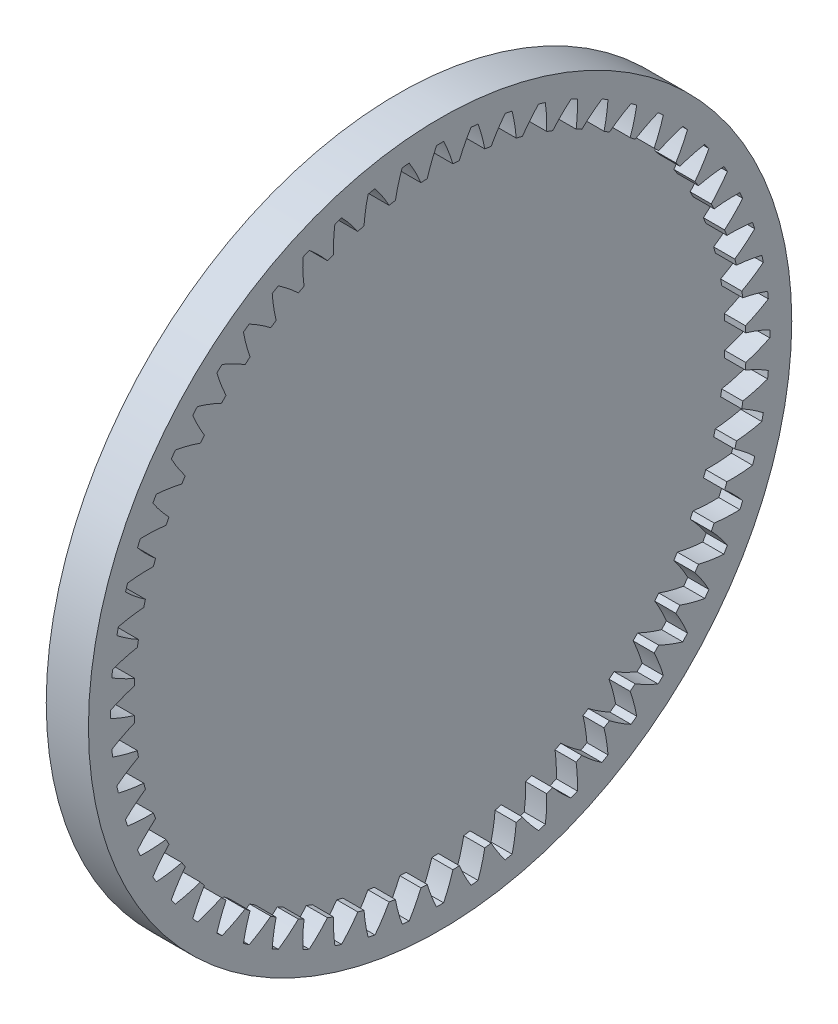
SolidWorks part; units mm, degrees
ref_plane "Plane1" through (0, 0, 0) normal (0, 0, 1) x (1, 0, 0)
ref_plane "Plane2" through (0, 0, 0) normal (0, 1, 0) x (1, 0, 0)
ref_plane "Plane3" through (0, 0, 0) normal (1, 0, 0) x (0, 0, -1)
other "Configuration Table"
sketch "HoldingSke" plane through (0, 0, 0) normal (0, 1, 0) x (1, 0, 0)
  line L0 (0, 0) -> (0.1667, -0.2887)
  line L1 (-15, 0) -> (100, 0) construction
  line L2 (0, 0) -> (-2.1039, 2.3779)
  line L3 (0, 0) -> (-11.863, 4.5341)
  line L4 (0, 0) -> (4.318, 7.479)
  line L5 (0, 0) -> (-23.7986, -8.8762)
  line L6 (0, 0) -> (-10.5278, -7.1032)
  line L7 (-2.1039, 2.3779) -> (3.3635, 27.1825)
  line L8 (-76.2, 5.3779) -> (-54.61, 5.3779)
  line L9 (-71.009, 38.7566) -> (-53.1078, 45.2721)
  line L10 (-76.2, 71.12) -> (104.1128, 71.12)
  line L11 (0, 0) -> (-12, 0)
  line L12 (-76.2, 101.6) -> (-76.093, 101.6)
  line L13 (24.9733, 27.94) -> (52.9518, 28.4284)
  line L14 (24.9733, 27.94) -> (24.9743, 27.94)
  line L15 (24.9733, 27.94) -> (100.4006, 29.5858)
  circle A0 centre (0, 0) radius 100
  circle A1 centre (0, 0) radius 12.7
  circle A2 centre (0, 0) radius 12.7
  dimension "Num_teeth" = 60
  dimension "Pitch_radius" = 180.3128
  dimension "Width" = 12
  dimension "Diameter" = 200
sketch "BasProSke" plane through (0, 0, 0) normal (0, 1, 0) x (1, 0, 0)
  line L0 (-10, 0) -> (60, 0) construction
  line L1 (0, 87) -> (0, 100)
  line L2 (0, 87) -> (12, 87)
  line L3 (12, 87) -> (12, 100)
  line L4 (12, 100) -> (0, 100)
  dimension "Thickness" = 12
  dimension "Diameter" = 200
revolve "Base-Revolve" add sketch "BasProSke" angle 360 about L0
sketch "TooCutSke" plane through (0, 0, 0) normal (1, 0, 0) x (0, 0, -1)
  line L3 (2.6234, 89.9618) -> (2.6234, 53.6633) construction
  line L4 (0, 0) -> (0, 59.563) construction
  line L5 (0, 0) -> (-3.576, 68.2339) construction
  line L6 (-39.5068, 74.1491) -> (33.8074, 77.9913) construction
  circle A0 centre (0, 0) radius 90 construction
  circle A1 centre (0, 0) radius 93.751 construction
  circle A2 centre (0, 0) radius 76.1151 construction
  circle A3 centre (0, 0) radius 86.9746 construction
  arc A4 (3.6494, 86.898) -> (1.0021, 93.7456) centre (-39.5068, 74.1491) ccw
  arc A5 (3.6494, 86.898) -> (-3.6494, 86.898) centre (0, 0) ccw
  arc A6 (1.0021, 93.7456) -> (-1.0021, 93.7456) centre (0, 0) ccw
  arc A7 (-1.0021, 93.7456) -> (-3.6494, 86.898) centre (39.5068, 74.1491) ccw
extrude "ToothCut" cut sketch "TooCutSke" along normal through all
fillet "Breaks" [suppressed] radius 0.3
fillet "RootFillets" [suppressed] radius 0.751
pattern_circular "TeethCuts" count 60 every 6 about axis through (-10, 0, 0) along (1, 0, 0) of "RootFillets", "Breaks", "ToothCut"
sketch "Sketch1" plane through (0, 0, 0) normal (-1, 0, 0) x (0, 0, 1)
  circle A0 centre (0, 0) radius 100
extrude "Boss-Extrude1" add sketch "Sketch1" against normal blind 6
equation "' \"Module@HoldingSke\" = 6.35"
equation "' \"Num_teeth@HoldingSke\" = 24"
equation "' \"Ap@HoldingSke\" =  14.5"
equation "' \"Ap@HoldingSke\" = 14.5"
equation "' \"Width@HoldingSke\" = 12"
equation "' \"Diameter@HoldingSke\" = 8 * 25.4"
equation "' \"Show_teeth@HoldingSke\" = 100"
equation "' \"Backlash@HoldingSke\" = 0.009 * 25.4"
equation "' \"Addendum_fac@HoldingSke\" = 1.0"
equation "' \"Dedendum_fac@HoldingSke\" = 1.25"
equation "' \"Dedendum_add@HoldingSke\" = 0.00005 * 25.4"
equation "' \"Clearance_fac@HoldingSke\" = 0.25"
equation "\"Pitch@HoldingSke\" = 1 / \"Module@HoldingSke\" "
equation "\"Overcut_dia@TooCutSke\" = (\"Num_teeth@HoldingSke\" - 2 * \"Addendum_fac@HoldingSke\") / \"Pitch@HoldingSke\" - 0.002 * 25.4"
equation "\"Pitch_dia@TooCutSke\" = \"Num_teeth@HoldingSke\" / \"Pitch@HoldingSke\""
equation "\"Base_dia@TooCutSke\" = \"Num_teeth@HoldingSke\" / \"Pitch@HoldingSke\" * cos((\"Ap@HoldingSke\"  * 3.14159265 / 180)) * 0.90"
equation "\"Root_dia@TooCutSke\" = \"Num_teeth@HoldingSke\"  / \"Pitch@HoldingSke\" + 2 *  \"Dedendum_fac@HoldingSke\"/ \"Pitch@HoldingSke\" + \"Dedendum_add@HoldingSke\" * 2"
equation "\"Half_ang@TooCutSke\" = 180 / \"Num_teeth@HoldingSke\""
equation "\"Half_CT@TooCutSke\" = \"Num_teeth@HoldingSke\" / \"Pitch@HoldingSke\" * sin((3.14159265 / 2 / \"Num_teeth@HoldingSke\")) / 2 + 10 * \"Backlash@HoldingSke\" / 4"
equation "\"Flank_rad@TooCutSke\" = \"Num_teeth@HoldingSke\" / \"Pitch@HoldingSke\" / 4"
equation "\"Radius@RootFillets\"= \"Clearance_fac@HoldingSke\" / \"Pitch@HoldingSke\" + \"Dedendum_add@HoldingSke\""
equation "\"Break_rad@Breaks\" = 0.02 / \"Pitch@HoldingSke\" * 5"
equation "\"Num_teeth@TeethCuts\" = int( \"Show_teeth@HoldingSke\" ) + 1"
equation "\"Num_teeth@TeethCuts\" = ((sgn( \"Num_teeth@TeethCuts\" - \"Num_teeth@HoldingSke\" )-1)*( \"Num_teeth@TeethCuts\" - \"Num_teeth@HoldingSke\" ))/-2+ \"Num_teeth@HoldingSke\""
equation "\"Num_teeth@TeethCuts\" = ((sgn( \"Num_teeth@TeethCuts\" - 2.0)+1)*( \"Num_teeth@TeethCuts\" - 2.0))/2 +2.0"
equation "\"Angle@TeethCuts\" = 360.0 / \"Num_teeth@HoldingSke\""
equation "\"Diameter@BasProSke\" = \"Num_teeth@HoldingSke\"  / \"Pitch@HoldingSke\" + 2 *  \"Dedendum_fac@HoldingSke\"/ \"Pitch@HoldingSke\" + \"Dedendum_add@HoldingSke\" * 2 + 0.002 * 25.4"
equation "\"Diameter@BasProSke\" = ((sgn( \"Diameter@BasProSke\"  - \"Diameter@HoldingSke\" )+1)*( \"Diameter@BasProSke\"  - \"Diameter@HoldingSke\" ))/2 + \"Diameter@HoldingSke\""
equation "\"Inside_diameter@BasProSke\" =  (\"Num_teeth@HoldingSke\" - 2 * \"Addendum_fac@HoldingSke\") / \"Pitch@HoldingSke\" "
equation "\"Thickness@BasProSke\"  = \"Width@HoldingSke\""
